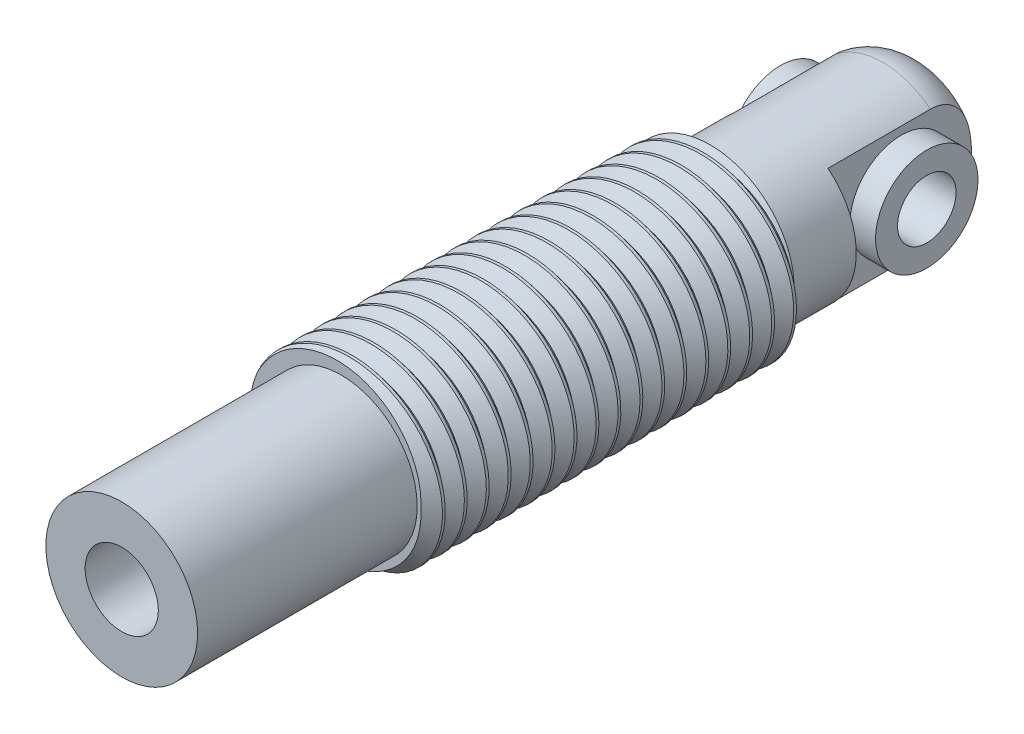
SolidWorks part; units mm, degrees
ref_plane "Piano frontale" through (0, 0, 0) normal (0, 0, 1) x (1, 0, 0)
ref_plane "Piano superiore" through (0, 0, 0) normal (0, 1, 0) x (1, 0, 0)
ref_plane "Piano destro" through (0, 0, 0) normal (1, 0, 0) x (0, 0, -1)
sketch "Schizzo1" plane through (0, 0, 0) normal (0, 0, 1) x (1, 0, 0)
  circle A0 centre (0, 0) radius 10.37
  dimension "D1" = 20.74
extrude "Estrusione-Estrusione1" add sketch "Schizzo1" along normal blind 110
fillet "Raccordo1" radius 6 1 edges at (10.37, 0, 0)
sketch "Schizzo2" plane through (0, 0, 0) normal (0, 0, -1) x (-1, 0, 0)
  line L0 (-21.7576, 0) -> (23.0501, 0) construction
  line L1 (0, 18.5801) -> (0, -18.4724) construction
  line L3 (11.5, -9) -> (6.5, -9)
  line L4 (11.5, -9) -> (11.5, 9)
  line L5 (11.5, 9) -> (6.5, 9)
  line L6 (6.5, -9) -> (6.5, 9)
  line L7 (11.5, -9) -> (6.5, 9) construction
  line L8 (11.5, 9) -> (6.5, -9) construction
  point P5 (9, 0)
  dimension "D1" = 6.5
  dimension "D2" = 18
  dimension "D3" = 5
extrude "Taglio-Estrusione1" cut sketch "Schizzo2" against normal blind 20
mirror "Specchia1" about plane through (0, 0, 0) normal (1, 0, 0) of "Taglio-Estrusione1"
sketch "Schizzo3" plane through (6.5, 0, 0) normal (1, 0, 0) x (0, 0, -1)
  line L0 (4.8737, 0) -> (-20, 0) construction
  line L1 (-20, -8.08) -> (-20, 8.08) construction
  line L2 (-10, 22.6066) -> (-10, -22.7298) construction
  circle A0 centre (-10, 0) radius 7
  dimension "D2" = 14
  dimension "D1" = 10
extrude "Estrusione-Estrusione2" add sketch "Schizzo3" along normal blind 3.5
mirror "Specchia2" about plane through (0, 0, 0) normal (1, 0, 0) of "Estrusione-Estrusione2"
sketch "Schizzo4" plane through (10, 0, 0) normal (1, 0, 0) x (0, 0, -1)
  line L0 (4.2741, 0) -> (-19.2377, 0) construction
  line L1 (-10, 13.4917) -> (-10, -14.6616) construction
  line L2 (0, -4.37) -> (0, 4.37) construction
  circle A0 centre (-10, 0) radius 4
  dimension "D2" = 8
  dimension "D1" = 10
extrude "Taglio-Estrusione2" cut sketch "Schizzo4" against normal blind 20
ref_plane "Piano1" through (0, 0, 80) normal (0, 0, 1) x (1, 0, 0)
sketch "Schizzo5" plane through (0, 0, 80) normal (0, 0, 1) x (1, 0, 0)
  circle A0 centre (0, 0) radius 12.5
  dimension "D1" = 25
extrude "Estrusione-Estrusione3" add sketch "Schizzo5" against normal blind 51
sketch "Schizzo7" plane through (0, 0, 29) normal (0, 0, -1) x (-1, 0, 0)
  circle A0 centre (0, 0) radius 12.5 construction
  circle A1 centre (0, 0) radius 12.5
curve "Elica/Spirale1" pitch 3 height 51 radius 12.5 centre (0, 0, 29) axis (0, 0, 1) start towards (1, 0, 0)
sketch "Schizzo9" plane through (0, 0, 0) normal (0, 1, 0) x (1, 0, 0)
  line L0 (12.5, -27.69) -> (12.5, -30.31)
  line L1 (12.5, -30.31) -> (10.87, -29)
  line L2 (10.87, -29) -> (12.5, -27.69)
  line L3 (10.87, -29) -> (12.5, -29) construction
  line L4 (10.37, -29) -> (-10.37, -29) construction
  spline S0 degree 3 poles (12.5, -29) (12.5, -29.0621) (11.8491, -29.1877) (9.0689, -29.375) (4.9081, -29.5625) (0, -29.75) (-4.9081, -29.9375) (-9.0689, -30.125) (-11.8491, -30.3125) (-12.8254, -30.5) (-11.8491, -30.6875) (-9.0689, -30.875) (-3.5211, -31.125) (3.5211, -31.375) (9.0689, -31.625) (11.8491, -31.8125) (12.8254, -32) (11.8491, -32.1875) (9.0689, -32.375) (3.5211, -32.625) (-3.5211, -32.875) (-9.0689, -33.125) (-11.8491, -33.3125) (-12.8254, -33.5) (-11.8491, -33.6875) (-9.0689, -33.875) (-3.5211, -34.125) (3.5211, -34.375) (9.0689, -34.625) (11.8491, -34.8125) (12.8254, -35) (11.8491, -35.1875) (9.0689, -35.375) (3.5211, -35.625) (-3.5211, -35.875) (-9.0689, -36.125) (-11.8491, -36.3125) (-12.8254, -36.5) (-11.8491, -36.6875) (-9.0689, -36.875) (-3.5211, -37.125) (3.5211, -37.375) (9.0689, -37.625) (11.8491, -37.8125) (12.8254, -38) (11.8491, -38.1875) (9.0689, -38.375) (3.5211, -38.625) (-3.5211, -38.875) (-9.0689, -39.125) (-11.8491, -39.3125) (-12.8254, -39.5) (-11.8491, -39.6875) (-9.0689, -39.875) (-3.5211, -40.125) (3.5211, -40.375) (9.0689, -40.625) (11.8491, -40.8125) (12.8254, -41) (11.8491, -41.1875) (9.0689, -41.375) (3.5211, -41.625) (-3.5211, -41.875) (-9.0689, -42.125) (-11.8491, -42.3125) (-12.8254, -42.5) (-11.8491, -42.6875) (-9.0689, -42.875) (-3.5211, -43.125) (3.5211, -43.375) (9.0689, -43.625) (11.8491, -43.8125) (12.8254, -44) (11.8491, -44.1875) (9.0689, -44.375) (3.5211, -44.625) (-3.5211, -44.875) (-9.0689, -45.125) (-11.8491, -45.3125) (-12.8254, -45.5) (-11.8491, -45.6875) (-9.0689, -45.875) (-3.5211, -46.125) (3.5211, -46.375) (9.0689, -46.625) (11.8491, -46.8125) (12.8254, -47) (11.8491, -47.1875) (9.0689, -47.375) (3.5211, -47.625) (-3.5211, -47.875) (-9.0689, -48.125) (-11.8491, -48.3125) (-12.8254, -48.5) (-11.8491, -48.6875) (-9.0689, -48.875) (-3.5211, -49.125) (3.5211, -49.375) (9.0689, -49.625) (11.8491, -49.8125) (12.8254, -50) (11.8491, -50.1875) (9.0689, -50.375) (3.5211, -50.625) (-3.5211, -50.875) (-9.0689, -51.125) (-11.8491, -51.3125) (-12.8254, -51.5) (-11.8491, -51.6875) (-9.0689, -51.875) (-3.5211, -52.125) (3.5211, -52.375) (9.0689, -52.625) (11.8491, -52.8125) (12.8254, -53) (11.8491, -53.1875) (9.0689, -53.375) (3.5211, -53.625) (-3.5211, -53.875) (-9.0689, -54.125) (-11.8491, -54.3125) (-12.8254, -54.5) (-11.8491, -54.6875) (-9.0689, -54.875) (-3.5211, -55.125) (3.5211, -55.375) (9.0689, -55.625) (11.8491, -55.8125) (12.8254, -56) (11.8491, -56.1875) (9.0689, -56.375) (3.5211, -56.625) (-3.5211, -56.875) (-9.0689, -57.125) (-11.8491, -57.3125) (-12.8254, -57.5) (-11.8491, -57.6875) (-9.0689, -57.875) (-3.5211, -58.125) (3.5211, -58.375) (9.0689, -58.625) (11.8491, -58.8125) (12.8254, -59) (11.8491, -59.1875) (9.0689, -59.375) (3.5211, -59.625) (-3.5211, -59.875) (-9.0689, -60.125) (-11.8491, -60.3125) (-12.8254, -60.5) (-11.8491, -60.6875) (-9.0689, -60.875) (-3.5211, -61.125) (3.5211, -61.375) (9.0689, -61.625) (11.8491, -61.8125) (12.8254, -62) (11.8491, -62.1875) (9.0689, -62.375) (3.5211, -62.625) (-3.5211, -62.875) (-9.0689, -63.125) (-11.8491, -63.3125) (-12.8254, -63.5) (-11.8491, -63.6875) (-9.0689, -63.875) (-3.5211, -64.125) (3.5211, -64.375) (9.0689, -64.625) (11.8491, -64.8125) (12.8254, -65) (11.8491, -65.1875) (9.0689, -65.375) (3.5211, -65.625) (-3.5211, -65.875) (-9.0689, -66.125) (-11.8491, -66.3125) (-12.8254, -66.5) (-11.8491, -66.6875) (-9.0689, -66.875) (-3.5211, -67.125) (3.5211, -67.375) (9.0689, -67.625) (11.8491, -67.8125) (12.8254, -68) (11.8491, -68.1875) (9.0689, -68.375) (3.5211, -68.625) (-3.5211, -68.875) (-9.0689, -69.125) (-11.8491, -69.3125) (-12.8254, -69.5) (-11.8491, -69.6875) (-9.0689, -69.875) (-3.5211, -70.125) (3.5211, -70.375) (9.0689, -70.625) (11.8491, -70.8125) (12.8254, -71) (11.8491, -71.1875) (9.0689, -71.375) (3.5211, -71.625) (-3.5211, -71.875) (-9.0689, -72.125) (-11.8491, -72.3125) (-12.8254, -72.5) (-11.8491, -72.6875) (-9.0689, -72.875) (-3.5211, -73.125) (3.5211, -73.375) (9.0689, -73.625) (11.8491, -73.8125) (12.8254, -74) (11.8491, -74.1875) (9.0689, -74.375) (3.5211, -74.625) (-3.5211, -74.875) (-9.0689, -75.125) (-11.8491, -75.3125) (-12.8254, -75.5) (-11.8491, -75.6875) (-9.0689, -75.875) (-3.5211, -76.125) (3.5211, -76.375) (9.0689, -76.625) (11.8491, -76.8125) (12.8254, -77) (11.8491, -77.1875) (9.0689, -77.375) (3.5211, -77.625) (-3.5211, -77.875) (-9.0689, -78.125) (-11.8491, -78.3125) (-12.8254, -78.5) (-11.8491, -78.6875) (-9.0689, -78.875) (-4.9081, -79.0625) (0, -79.25) (4.9081, -79.4375) (9.0689, -79.625) (11.8491, -79.8123) (12.5, -79.9379) (12.5, -80) knots 0 0 0 0 0.003676 0.007353 0.011029 0.014706 0.018382 0.022059 0.025735 0.029412 0.033088 0.036765 0.040441 0.047794 0.051471 0.055147 0.058824 0.0625 0.066176 0.069853 0.077206 0.080882 0.084559 0.088235 0.091912 0.095588 0.099265 0.106618 0.110294 0.113971 0.117647 0.121324 0.125 0.128676 0.136029 0.139706 0.143382 0.147059 0.150735 0.154412 0.158088 0.165441 0.169118 0.172794 0.176471 0.180147 0.183824 0.1875 0.194853 0.198529 0.202206 0.205882 0.209559 0.213235 0.216912 0.224265 0.227941 0.231618 0.235294 0.238971 0.242647 0.246324 0.253676 0.257353 0.261029 0.264706 0.268382 0.272059 0.275735 0.283088 0.286765 0.290441 0.294118 0.297794 0.301471 0.305147 0.3125 0.316176 0.319853 0.323529 0.327206 0.330882 0.334559 0.341912 0.345588 0.349265 0.352941 0.356618 0.360294 0.363971 0.371324 0.375 0.378676 0.382353 0.386029 0.389706 0.393382 0.400735 0.404412 0.408088 0.411765 0.415441 0.419118 0.422794 0.430147 0.433824 0.4375 0.441176 0.444853 0.448529 0.452206 0.459559 0.463235 0.466912 0.470588 0.474265 0.477941 0.481618 0.488971 0.492647 0.496324 0.5 0.503676 0.507353 0.511029 0.518382 0.522059 0.525735 0.529412 0.533088 0.536765 0.540441 0.547794 0.551471 0.555147 0.558824 0.5625 0.566176 0.569853 0.577206 0.580882 0.584559 0.588235 0.591912 0.595588 0.599265 0.606618 0.610294 0.613971 0.617647 0.621324 0.625 0.628676 0.636029 0.639706 0.643382 0.647059 0.650735 0.654412 0.658088 0.665441 0.669118 0.672794 0.676471 0.680147 0.683824 0.6875 0.694853 0.698529 0.702206 0.705882 0.709559 0.713235 0.716912 0.724265 0.727941 0.731618 0.735294 0.738971 0.742647 0.746324 0.753676 0.757353 0.761029 0.764706 0.768382 0.772059 0.775735 0.783088 0.786765 0.790441 0.794118 0.797794 0.801471 0.805147 0.8125 0.816176 0.819853 0.823529 0.827206 0.830882 0.834559 0.841912 0.845588 0.849265 0.852941 0.856618 0.860294 0.863971 0.871324 0.875 0.878676 0.882353 0.886029 0.889706 0.893382 0.900735 0.904412 0.908088 0.911765 0.915441 0.919118 0.922794 0.930147 0.933824 0.9375 0.941176 0.944853 0.948529 0.952206 0.959559 0.963235 0.966912 0.970588 0.974265 0.977941 0.981618 0.985294 0.988971 0.992647 0.996324 1 1 1 1 construction
  dimension "D1" = 1.63
  dimension "D2" = 2.62
sweep "Taglia-Sweep2" cut profiles "Schizzo9" path "Elica/Spirale1" align with end faces yes
sketch "Schizzo10" plane through (0, 0, 110) normal (0, 0, 1) x (1, 0, 0)
  circle A0 centre (0, 0) radius 5
  dimension "D1" = 10
extrude "Taglio-Estrusione3" cut sketch "Schizzo10" against normal blind 60
